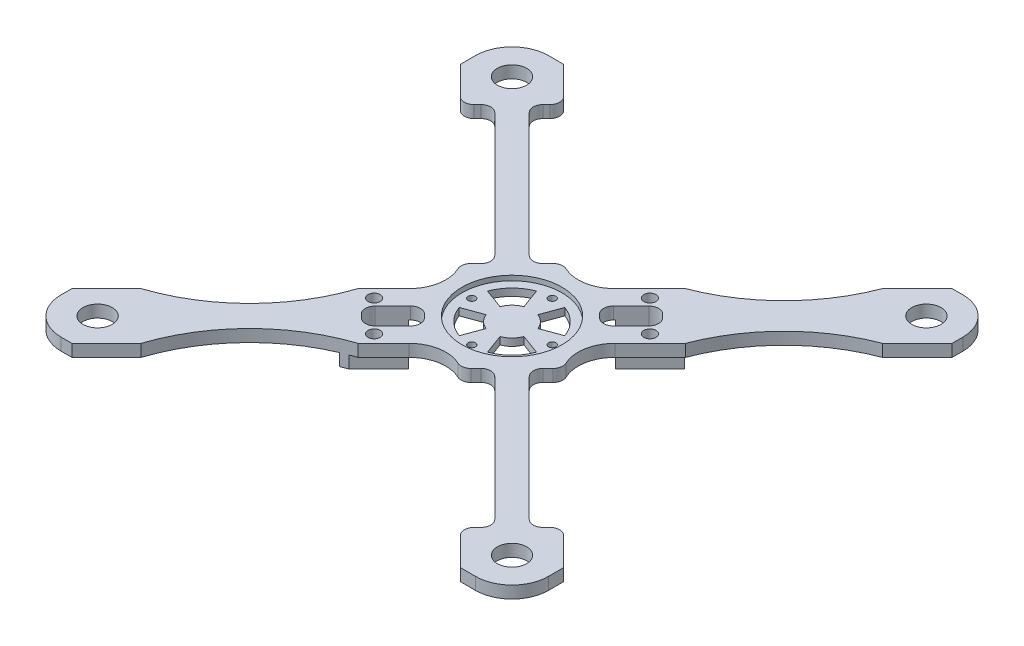
SolidWorks part; units mm, degrees
ref_plane "前基準面" through (0, 0, 0) normal (0, 0, 1) x (1, 0, 0)
ref_plane "上基準面" through (0, 0, 0) normal (0, 1, 0) x (1, 0, 0)
ref_plane "右基準面" through (0, 0, 0) normal (1, 0, 0) x (0, 0, -1)
sketch "草圖1" plane through (0, 0, 0) normal (0, 1, 0) x (1, 0, 0)
  line L0 (-1000, 0) -> (49000, 0) construction
  line L1 (-100, -100) -> (100, -100)
  line L2 (-100, -100) -> (-100, 100)
  line L3 (-100, 100) -> (100, 100)
  line L4 (100, -100) -> (100, 100)
  line L5 (-100, -100) -> (100, 100) construction
  line L6 (-100, 100) -> (100, -100) construction
  line L7 (0, -1000) -> (0, 49000) construction
  circle A0 centre (85, 85) radius 6
  circle A1 centre (-85, 85) radius 6
  circle A2 centre (85, -85) radius 6
  circle A3 centre (-85, -85) radius 6
  point P0 (0, 0)
  dimension "D4" = 12
  dimension "D1" = 200
  dimension "D2" = 200
  dimension "D3" = 15
  dimension "D5" = 15
extrude "填料-伸長1" add sketch "草圖1" along normal blind 5
sketch "草圖3" plane through (0, 5, 0) normal (0, 1, 0) x (1, 0, 0)
  circle A0 centre (0, 0) radius 20.5
  dimension "D1" = 41
extrude "除料-伸長1" cut sketch "草圖3" against normal blind 2
sketch "草圖4" plane through (0, 3, 0) normal (0, 1, 0) x (1, 0, 0)
  line L0 (0, -1000) -> (0, 49000) construction
  line L1 (-1000, 0) -> (49000, 0) construction
  circle A1 centre (-16.5, 0) radius 1.5
  circle A3 centre (16.5, 0) radius 1.5
  circle A6 centre (0, 16.5) radius 1.5
  circle A8 centre (0, -16.5) radius 1.5
  dimension "D6" = 33
  dimension "D5" = 33
extrude "除料-伸長2" cut sketch "草圖4" against normal through all
sketch "草圖6" plane through (0, 0, 0) normal (0, -1, 0) x (1, 0, 0)
  line L0 (0, 0) -> (-95.4594, 95.4594) construction
  line L1 (-44.1942, 26.5165) -> (-30.052, 12.3744)
  line L2 (26.5165, -44.1942) -> (44.1942, -26.5165)
  line L3 (44.1942, -26.5165) -> (30.052, -12.3744)
  line L4 (-26.5165, 44.1942) -> (-44.1942, 26.5165)
  line L5 (0, 0) -> (57.7931, 57.7931) construction
  line L6 (-12.3744, 30.052) -> (-30.052, 12.3744)
  line L7 (30.052, -12.3744) -> (12.3744, -30.052)
  line L8 (-12.3744, 30.052) -> (-26.5165, 44.1942)
  line L9 (12.3744, -30.052) -> (26.5165, -44.1942)
  circle A0 centre (-21.9203, 34.6482) radius 2.5
  circle A1 centre (34.6482, -21.9203) radius 2.5
  circle A2 centre (21.9203, -34.6482) radius 2.5
  circle A3 centre (-34.6482, 21.9203) radius 2.5
  dimension "D3" = 5
  dimension "D1" = 25
  dimension "D2" = 100
  dimension "D4" = 18
  dimension "D5" = 10
  dimension "D6" = 20
extrude "填料-伸長2" add sketch "草圖6" along normal blind 5
sketch "草圖5" plane through (0, 5, 0) normal (0, 1, 0) x (1, 0, 0)
  line L0 (0, 0) -> (100, 100) construction
  line L1 (15.1023, -22.1734) -> (71.5809, -78.652)
  line L4 (-20.3293, -0.8839) -> (-29.2444, 8.0312)
  line L5 (-78.7868, 100) -> (80.5546, 100)
  line L6 (0, 0) -> (-100, 100) construction
  line L9 (0.8839, 20.3293) -> (-8.0312, 29.2444)
  line L12 (-20.3293, -0.8839) -> (-41.3133, -21.8678)
  line L26 (0.8839, 20.3293) -> (25.8571, 45.3025)
  line L28 (-85.8079, -66.3625) -> (-100, -80.5546)
  line L29 (64.5099, -85.7231) -> (71.5809, -78.652)
  line L30 (64.5099, -85.7231) -> (78.7868, -100)
  line L31 (-0.8839, -20.3293) -> (0.8839, 20.3293) construction
  line L32 (-20.3293, -0.8839) -> (20.3293, 0.8839) construction
  line L33 (100, 100) -> (-100, 100) construction
  line L34 (-100, 78.7868) -> (-100, -80.5546)
  line L41 (-85.7231, 64.5099) -> (-100, 78.7868)
  line L42 (-64.5099, 85.7231) -> (-78.7868, 100)
  line L43 (66.2776, 85.7231) -> (80.5546, 100)
  line L52 (14.4255, 21.4966) -> (27.3554, 34.4264)
  line L53 (27.3554, 34.4264) -> (34.4264, 27.3554)
  line L54 (34.4264, 27.3554) -> (21.4966, 14.4255)
  line L55 (21.4966, 14.4255) -> (14.4255, 21.4966)
  line L60 (-14.4255, -21.4966) -> (-27.3554, -34.4264)
  line L61 (-27.3554, -34.4264) -> (-34.4264, -27.3554)
  line L62 (-34.4264, -27.3554) -> (-21.4966, -14.4255)
  line L63 (-21.4966, -14.4255) -> (-14.4255, -21.4966)
  line L64 (-15.8662, 5.8142) -> (-7.7514, 2.8405)
  line L65 (-5.8142, 15.8662) -> (-2.8405, 7.7514)
  line L66 (15.8662, 5.8142) -> (7.7514, 2.8405)
  line L67 (5.8142, 15.8662) -> (2.8405, 7.7514)
  line L68 (5.8142, -15.8662) -> (2.8405, -7.7514)
  line L69 (15.8662, -5.8142) -> (7.7514, -2.8405)
  line L70 (-15.8662, -5.8142) -> (-7.7514, -2.8405)
  line L71 (-5.8142, -15.8662) -> (-2.8405, -7.7514)
  line L72 (-85.7231, 64.5099) -> (-78.652, 71.5809)
  line L73 (-8.0312, 29.2444) -> (-15.1023, 22.1734)
  line L74 (-22.1734, 15.1023) -> (-78.652, 71.5809)
  line L75 (-15.1023, 22.1734) -> (-71.5809, 78.652)
  line L76 (-22.1734, 15.1023) -> (-29.2444, 8.0312)
  line L77 (-71.5809, 78.652) -> (-64.5099, 85.7231)
  line L78 (78.7868, -100) -> (-80.5546, -100)
  line L79 (-66.3625, -85.8079) -> (-80.5546, -100)
  line L80 (-0.8839, -20.3293) -> (-21.8678, -41.3133)
  line L81 (-0.8839, -20.3293) -> (8.0312, -29.2444)
  line L82 (15.1023, -22.1734) -> (8.0312, -29.2444)
  line L83 (20.3293, 0.8839) -> (45.3025, 25.8571)
  line L84 (85.7231, 66.2776) -> (100, 80.5546)
  line L85 (100, -78.7868) -> (100, 80.5546)
  line L86 (85.7231, -64.5099) -> (100, -78.7868)
  line L87 (78.652, -71.5809) -> (85.7231, -64.5099)
  line L88 (22.1734, -15.1023) -> (78.652, -71.5809)
  line L89 (29.2444, -8.0312) -> (22.1734, -15.1023)
  line L90 (20.3293, 0.8839) -> (29.2444, -8.0312)
  arc A0 (-85.8079, -66.3625) -> (-41.3133, -21.8678) centre (-107.7766, 0.1009) ccw
  arc A2 (25.8571, 45.3025) -> (66.2776, 85.7231) centre (0.8839, 110.6962) ccw
  arc A8 (-66.3625, -85.8079) -> (-21.8678, -41.3133) centre (0.1009, -107.7766) cw
  arc A9 (-2.8405, 7.7514) -> (-7.7514, 2.8405) centre (0, 0) ccw
  arc A10 (-5.8142, 15.8662) -> (-15.8662, 5.8142) centre (0, 0) ccw
  arc A11 (-15.8662, -5.8142) -> (-5.8142, -15.8662) centre (0, 0) ccw
  arc A12 (-7.7514, -2.8405) -> (-2.8405, -7.7514) centre (0, 0) ccw
  arc A13 (2.8405, -7.7514) -> (7.7514, -2.8405) centre (0, 0) ccw
  arc A14 (5.8142, -15.8662) -> (15.8662, -5.8142) centre (0, 0) ccw
  arc A15 (7.7514, 2.8405) -> (2.8405, 7.7514) centre (0, 0) ccw
  arc A16 (15.8662, 5.8142) -> (5.8142, 15.8662) centre (0, 0) ccw
  arc A17 (45.3025, 25.8571) -> (85.7231, 66.2776) centre (110.6962, 0.8839) cw
  point P49 (0, 0)
  point P66 (0, 0)
  point P85 (0, 0)
  dimension "D2" = 10
  dimension "D1" = 30
  dimension "D7" = 4
extrude "除料-伸長3" cut sketch "草圖5" against normal through all
fillet "圓角1" radius 15 8 edges at (-100, 2.5, 100) (-100, 2.5, -100) (100, 2.5, -100) (100, 2.5, 100) (-20.3293, 1.5, 0.8839) (0.8839, 1.5, -20.3293) (20.3293, 1.5, -0.8839) (-0.8839, 1.5, 20.3293)
sketch "草圖7" plane through (0, 5, 0) normal (0, 1, 0) x (1, 0, 0)
  line L0 (0, 0) -> (48.5764, 48.5764) construction
  line L1 (0, 0) -> (-38.1772, 38.1772) construction
  circle A0 centre (21.9203, 34.6482) radius 2.5
  circle A1 centre (34.6482, 21.9203) radius 2.5
  circle A2 centre (-21.9203, -34.6482) radius 2.5
  circle A3 centre (-34.6482, -21.9203) radius 2.5
  dimension "D1" = 5
extrude "除料-伸長4" cut sketch "草圖7" against normal through all
fillet "圓角2" radius 4 24 edges at (14.4255, 2.5, -21.4966) (21.4966, 2.5, -14.4255) (34.4264, 0, -27.3554) (27.3554, 0, -34.4264) (-21.4966, 2.5, 14.4255) (-34.4264, 0, 27.3554) (-14.4255, 2.5, 21.4966) (-27.3554, 0, 34.4264) (-85.7231, 2.5, -64.5099) (-78.652, 2.5, -71.5809) (-64.5099, 2.5, -85.7231) (-71.5809, 2.5, -78.652) (78.652, 2.5, 71.5809) (85.7231, 2.5, 64.5099) (64.5099, 2.5, 85.7231) (71.5809, 2.5, 78.652) (-15.1023, 2.5, -22.1734) (-22.1734, 2.5, -15.1023) (15.1023, 2.5, 22.1734) (22.1734, 2.5, 15.1023) (29.2444, 2.5, 8.0312) (8.0312, 2.5, 29.2444) (-8.0312, 2.5, -29.2444) (-29.2444, 2.5, -8.0312)
